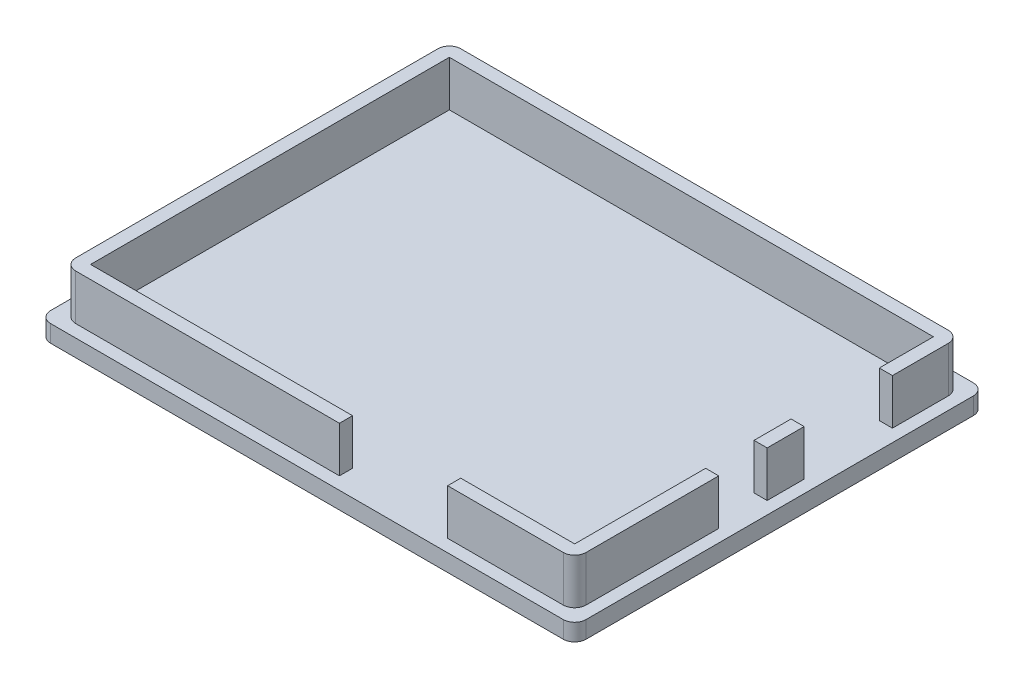
SolidWorks part; units mm, degrees
ref_plane "Plano frontal" through (0, 0, 0) normal (0, 0, 1) x (1, 0, 0)
ref_plane "Plano superior" through (0, 0, 0) normal (0, 1, 0) x (1, 0, 0)
ref_plane "Plano direito" through (0, 0, 0) normal (1, 0, 0) x (0, 0, -1)
sketch "Esboço1" plane through (0, 0, 0) normal (0, 1, 0) x (1, 0, 0)
  line L1 (-47, -36) -> (47, -36)
  line L2 (-47, -36) -> (-47, 36)
  line L3 (-47, 36) -> (47, 36)
  line L4 (47, -36) -> (47, 36)
  line L5 (-47, -36) -> (47, 36) construction
  line L6 (-47, 36) -> (47, -36) construction
  point P0 (0, 0)
  dimension "D1" = 94
  dimension "D2" = 72
extrude "Ressalto-extrusão1" add sketch "Esboço1" along normal mid plane 3
sketch "Esboço2" plane through (0, 1.5, 0) normal (0, 1, 0) x (1, 0, 0)
  line L8 (44.8, -33.8) -> (44.8, 33.8)
  line L9 (44.8, 33.8) -> (-44.8, 33.8)
  line L10 (-44.8, 33.8) -> (-44.8, -33.8)
  line L11 (-44.8, -33.8) -> (44.8, -33.8)
  line L12 (44.8, -33.8) -> (44.8, 33.8)
  line L13 (44.8, 33.8) -> (-44.8, 33.8)
  line L14 (-44.8, 33.8) -> (-44.8, -33.8)
  line L15 (-44.8, -33.8) -> (44.8, -33.8)
  line L20 (42.5, -31.5) -> (42.5, 31.5)
  line L21 (42.5, 31.5) -> (-42.5, 31.5)
  line L22 (-42.5, 31.5) -> (-42.5, -31.5)
  line L23 (-42.5, -31.5) -> (42.5, -31.5)
  line L24 (42.5, -31.5) -> (42.5, 31.5)
  line L25 (42.5, 31.5) -> (-42.5, 31.5)
  line L26 (-42.5, 31.5) -> (-42.5, -31.5)
  line L27 (-42.5, -31.5) -> (42.5, -31.5)
  dimension "D1" = 2.2
  dimension "D2" = 4.5
extrude "Ressalto-extrusão2" add sketch "Esboço2" along normal blind 8 contours L12 L13 L14 L15 | L24 L25 L26 L27
fillet "Filete1" radius 2 8 edges at (47, 0, 36) (44.8, 5.5, 33.8) (47, 0, -36) (44.8, 5.5, -33.8) (-47, 0, -36) (-44.8, 5.5, -33.8) (-44.8, 5.5, 33.8) (-47, 0, 36)
sketch "Esboço3" plane through (42.5, 0, 0) normal (-1, 0, 0) x (0, 0, 1)
  line L0 (31.5, 9.5) -> (-31.5, 9.5) construction
  line L1 (-22, 1.5) -> (-6.5, 1.5)
  line L2 (-22, 1.5) -> (-22, 9.5)
  line L3 (-22, 9.5) -> (-6.5, 9.5)
  line L4 (-6.5, 1.5) -> (-6.5, 9.5)
  line L5 (-22, 1.5) -> (-6.5, 9.5) construction
  line L6 (-22, 9.5) -> (-6.5, 1.5) construction
  line L7 (31.5, 1.5) -> (-31.5, 1.5) construction
  line L8 (-31.5, 9.5) -> (-31.5, 1.5) construction
  point P0 (-14.25, 5.5)
  point P7 (-11.0152, 1.5)
  dimension "D1" = 9.5
  dimension "D2" = 15.5
extrude "Corte-extrusão1" cut sketch "Esboço3" against normal up to surface (4.5 mm away) up to face at (47, 0, 0)
sketch "Esboço4" plane through (42.5, 0, 0) normal (-1, 0, 0) x (0, 0, 1)
  line L0 (31.5, 1.5) -> (-6.5, 1.5) construction
  line L1 (0, 1.5) -> (8.5, 1.5)
  line L2 (0, 1.5) -> (0, 9.5)
  line L3 (0, 9.5) -> (8.5, 9.5)
  line L4 (8.5, 1.5) -> (8.5, 9.5)
  line L5 (31.5, 9.5) -> (-6.5, 9.5) construction
  line L6 (-31.5, 9.5) -> (-31.5, 1.5) construction
  dimension "D1" = 31.5
  dimension "D2" = 8.5
extrude "Corte-extrusão2" cut sketch "Esboço4" against normal up to surface (4.5 mm away) up to face at (47, 0, 0)
sketch "Esboço5" plane through (0, 0, 31.5) normal (0, 0, -1) x (-1, 0, 0)
  line L0 (42.5, 1.5) -> (-42.5, 1.5) construction
  line L1 (-22.5, 1.5) -> (-3.5, 1.5)
  line L2 (-22.5, 1.5) -> (-22.5, 9.5)
  line L3 (-22.5, 9.5) -> (-3.5, 9.5)
  line L4 (-3.5, 1.5) -> (-3.5, 9.5)
  line L5 (42.5, 9.5) -> (-42.5, 9.5) construction
  line L6 (-42.5, 9.5) -> (-42.5, 1.5) construction
  dimension "D1" = 39
  dimension "D2" = 19
extrude "Corte-extrusão3" cut sketch "Esboço5" against normal up to surface (4.5 mm away) up to face at (0, 0, 36)
